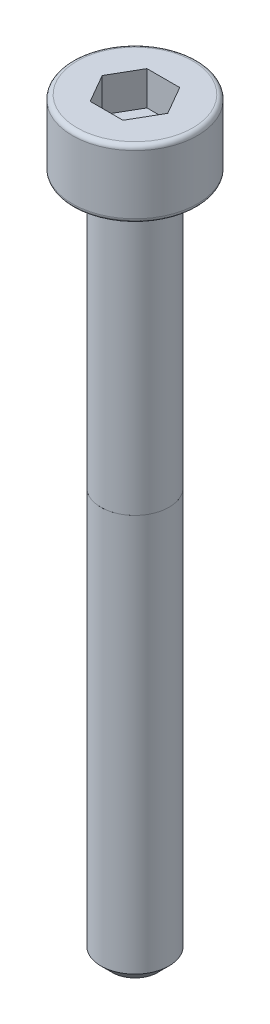
SolidWorks part; units mm, degrees
ref_plane "Front Plane" through (0, 0, 0) normal (0, 0, 1) x (1, 0, 0)
ref_plane "Top Plane" through (0, 0, 0) normal (0, 1, 0) x (1, 0, 0)
ref_plane "Right Plane" through (0, 0, 0) normal (1, 0, 0) x (0, 0, -1)
sketch "Sketch1" plane through (0, 0, 0) normal (0, 1, 0) x (1, 0, 0)
  circle A0 centre (0, 0) radius 2.75
  dimension "D1" = 5.5
extrude "Boss-Extrude1" add sketch "Sketch1" against normal blind 3
sketch "Sketch2" plane through (0, 0, 0) normal (0, 1, 0) x (1, 0, 0)
  line L1 (1.4434, 0) -> (0.7217, 1.25)
  line L2 (0.7217, 1.25) -> (-0.7217, 1.25)
  line L3 (-0.7217, 1.25) -> (-1.4434, 0)
  line L4 (-1.4434, 0) -> (-0.7217, -1.25)
  line L5 (-0.7217, -1.25) -> (0.7217, -1.25)
  line L6 (0.7217, -1.25) -> (1.4434, 0)
  circle A0 centre (0, 0) radius 1.25 construction
  dimension "D1" = 2.5
extrude "Cut-Extrude1" cut sketch "Sketch2" against normal blind 1.5
sketch "Sketch3" plane through (0, -3, 0) normal (0, -1, 0) x (1, 0, 0)
  circle A0 centre (0, 0) radius 1.5
  dimension "D1" = 3
extrude "Boss-Extrude2" add sketch "Sketch3" along normal blind 12
sketch "Sketch4" plane through (0, -15, 0) normal (0, -1, 0) x (1, 0, 0)
  circle A0 centre (0, 0) radius 1.5
  circle A1 centre (0, 0) radius 1.5 construction
extrude "Boss-Extrude3" add sketch "Sketch4" along normal blind 18 separate body
chamfer "Chamfer1" distance 0.5 angle 45 1 edges at (0, -33, -1.5)
fillet "Fillet1" radius 0.2 2 edges at (0, -3, 2.75) (0, 0, 2.75)
